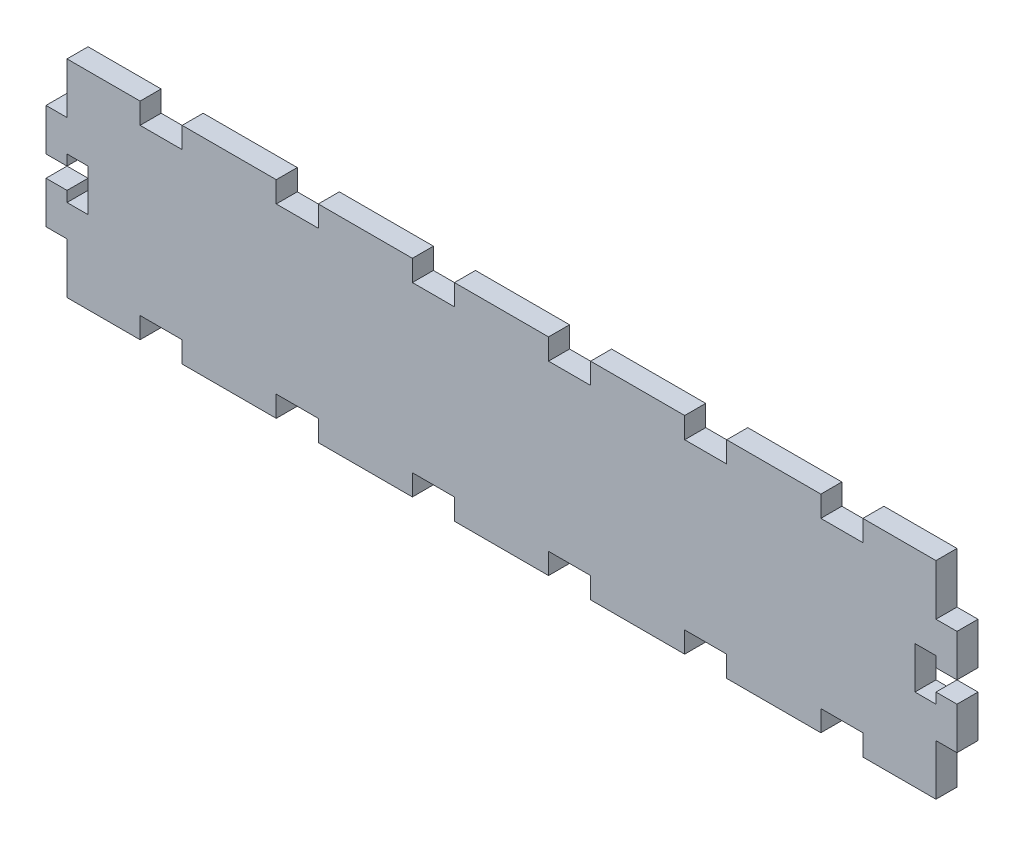
SolidWorks part; units mm, degrees
ref_plane "Front Plane" through (0, 0, 0) normal (0, 0, 1) x (1, 0, 0)
ref_plane "Top Plane" through (0, 0, 0) normal (0, 1, 0) x (1, 0, 0)
ref_plane "Right Plane" through (0, 0, 0) normal (1, 0, 0) x (0, 0, -1)
sketch "Sketch2" plane through (0, 0, 0) normal (0, 1, 0) x (1, 0, 0)
  line L0 (0, 0) -> (0, 6) construction
  dimension "D1" = 6
sketch "Sketch1" plane through (0, 0, 0) normal (0, 0, 1) x (1, 0, 0)
  line L1 (-130, -29.5) -> (130, -29.5)
  line L2 (-130, -29.5) -> (-130, 29.5)
  line L3 (-130, 29.5) -> (130, 29.5)
  line L4 (130, -29.5) -> (130, 29.5)
  line L5 (-130, -29.5) -> (130, 29.5) construction
  line L6 (-130, 29.5) -> (130, -29.5) construction
  point P0 (0, 0)
  dimension "D1" = 260
  dimension "D2" = 59
extrude "Boss-Extrude1" add sketch "Sketch1" against normal up to vertex (6 mm away) contours L2 L3 L4 L1 up to point (0, 0, -6)
sketch "Sketch3" plane through (0, 0, 0) normal (0, 0, 1) x (1, 0, 0)
  line L0 (-130, -29.5) -> (-130, 29.5) construction
  line L1 (-130, 15) -> (-124, 15) construction
  line L2 (-130, 15) -> (-130, 3) construction
  line L3 (-130, 3) -> (-124, 3) construction
  line L4 (-124, 15) -> (-124, 3) construction
  line L5 (-118, -6) -> (-118, -29.5) construction
  line L6 (-124, 3) -> (-130, 3)
  line L7 (-124, 3) -> (-124, -3)
  line L8 (-124, -3) -> (-130, -3)
  line L9 (-130, 3) -> (-130, -3)
  line L10 (-130, -3) -> (-124, -3) construction
  line L11 (-130, -3) -> (-130, -15) construction
  line L12 (-130, -15) -> (-124, -15) construction
  line L13 (-124, -3) -> (-124, -15) construction
  line L14 (-124, 15) -> (-130, 15)
  line L15 (-124, 15) -> (-124, 29.5)
  line L16 (-124, 29.5) -> (-130, 29.5)
  line L17 (-130, 15) -> (-130, 29.5)
  line L18 (-124, -15) -> (-130, -15)
  line L19 (-124, -15) -> (-124, -29.5)
  line L20 (-124, -29.5) -> (-130, -29.5)
  line L21 (-130, -15) -> (-130, -29.5)
  line L22 (-124, 6) -> (-118, 6)
  line L23 (-124, 6) -> (-124, -6)
  line L24 (-124, -6) -> (-118, -6)
  line L25 (-118, 6) -> (-118, -6)
  line L26 (-130, -29.5) -> (130, -29.5) construction
  line L27 (-118, 6) -> (-118, 29.5) construction
  line L28 (-130, 29.5) -> (130, 29.5) construction
  line L29 (0, 0) -> (0, -29.5) construction
  line L30 (-91.1429, -23.5) -> (-64.2857, -23.5) construction
  line L31 (-52.2857, -23.5) -> (-25.4286, -23.5) construction
  line L32 (-52.2857, -23.5) -> (-64.2857, -23.5)
  line L33 (-52.2857, -23.5) -> (-52.2857, -29.5)
  line L34 (-52.2857, -29.5) -> (-64.2857, -29.5)
  line L35 (-64.2857, -23.5) -> (-64.2857, -29.5)
  line L36 (-13.4286, -23.5) -> (-25.4286, -23.5)
  line L37 (-13.4286, -23.5) -> (-13.4286, -29.5)
  line L38 (-13.4286, -29.5) -> (-25.4286, -29.5)
  line L39 (-25.4286, -23.5) -> (-25.4286, -29.5)
  line L40 (-91.1429, -23.5) -> (-103.1429, -23.5)
  line L41 (-91.1429, -23.5) -> (-91.1429, -29.5)
  line L42 (-91.1429, -29.5) -> (-103.1429, -29.5)
  line L43 (-103.1429, -23.5) -> (-103.1429, -29.5)
  line L44 (-13.4286, -23.5) -> (13.4286, -23.5) construction
  line L45 (-103.1429, -23.5) -> (-130, -23.5) construction
  line L46 (-130, -23.5) -> (-130, -29.5) construction
  point P32 (0, -23.5)
  dimension "D1" = 6
  dimension "D2" = 12
  dimension "D3" = 6
  dimension "D4" = 12
extrude "Cut-Extrude1" cut sketch "Sketch3" against normal through all contours L25 L22 L23 L7 L24 | L6 L9 L8 L7 | L17 L14 L15 L16 | L18 L21 L20 L19 region at (-127, 0, 0) region at (-121, 0, 0) region at (-127, 22.25, 0) region at (-127, -22.25, 0)
extrude "Cut-Extrude2" cut sketch "Sketch3<3>" against normal through all contours L40 L43 L42 L41 | L32 L35 L34 L33 | L36 L39 L38 L37 region at (-58.2857, -26.5, 0) region at (-19.4286, -26.5, 0) region at (-97.1429, -26.5, 0)
sketch "Sketch3<3>" plane through (0, 0, 0) normal (0, 0, 1) x (1, 0, 0) same geometry as "Sketch3"
mirror "Mirror1" about plane through (0, 0, 0) normal (1, 0, 0) of "Cut-Extrude2" second plane through (0, 0, 0) second plane normal (0, 1, 0)
mirror "Mirror2" about plane through (0, 0, 0) normal (1, 0, 0) of "Cut-Extrude1"
equation "\"t_wood\"= 6' Thickness of the wood"
equation "\"t_glass\"= 2.5'Thickness of glass panels"
equation "\"w_glass\"= 248"
equation "\"h_glass\"= 167"
equation "\"h_food_internal\" = 60"
equation "\"entry_height\"= 20"
equation "\"entry diameter\"= 8"
equation "\"glass_bottom_overlap\"= 8"
equation "\"default_finger_size\"= 12"
equation "\"brood_depth\"= 42"
equation "\"outer_box_depth\" = \"brood_depth\" + ( 2 * \"t_glass\" ) + ( 2 * \"t_wood\" )"
equation "\"outer_box_width\"= \"w_glass\" + ( 2 * \"t_wood\" )"
equation "\"food_top_clearance\"= 10"
equation "\"outer_box_height\"= \"t_wood\" + \"h_glass\" + \"t_wood\" + \"h_food_internal\" + \"food_top_clearance\" + \"t_wood\""
equation "\"food_internal_depth\"= \"brood_depth\" + \"t_glass\" + \"t_glass\" - \"t_wood\" - \"t_wood\""
equation "\"food_channel_clearance_width\"= 14"
equation "\"bar_top_play\"= 4.5"
equation "\"bar_entry_angle\"= 10"
equation "\"bar_width\"= 20"
equation "\"entry_disk_play\"= 0.3"
equation "\"D1@Sketch2\"=\"t_wood\""
equation "\"D1@Sketch1\"=\"outer_box_width\""
equation "\"D2@Sketch1\"=\"outer_box_depth\""
equation "\"D1@Sketch3\"=\"t_wood\""
equation "\"D2@Sketch3\"=\"default_finger_size\""
equation "\"D3@Sketch3\"=\"t_wood\""
equation "\"D4@Sketch3\"=\"default_finger_size\""
